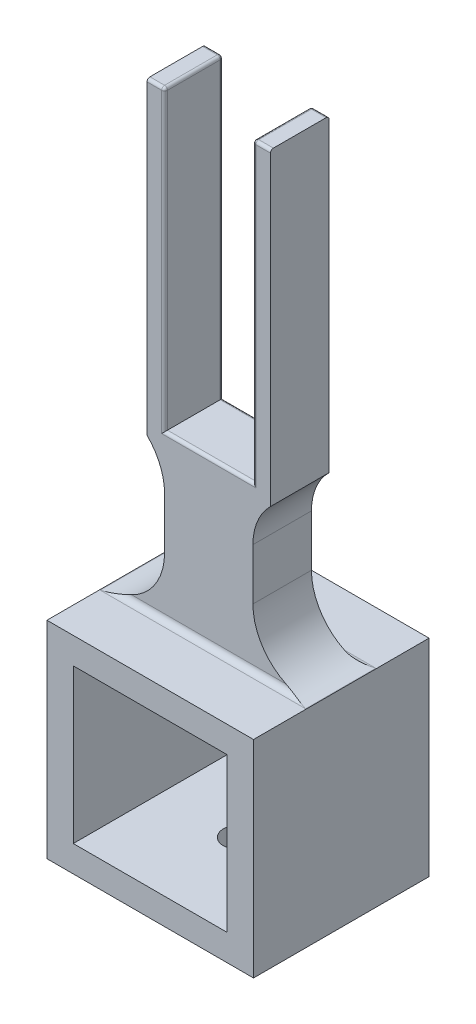
SolidWorks part; units mm, degrees
ref_plane "Front Plane" through (0, 0, 0) normal (0, 0, 1) x (1, 0, 0)
ref_plane "Top Plane" through (0, 0, 0) normal (0, 1, 0) x (1, 0, 0)
ref_plane "Right Plane" through (0, 0, 0) normal (1, 0, 0) x (0, 0, -1)
sketch "Sketch1" plane through (0, 0, 0) normal (0, 0, 1) x (1, 0, 0)
  line L0 (-12.5, -83.55) -> (-12.5, -58.55) construction
  line L1 (12.5, -83.55) -> (-12.5, -83.55) construction
  line L2 (12.5, -58.55) -> (12.5, -83.55) construction
  line L3 (-12.5, -58.55) -> (12.5, -58.55) construction
  line L4 (-12.65, -83.7) -> (-12.65, -58.4)
  line L5 (-12.65, -58.4) -> (12.65, -58.4)
  line L6 (12.65, -58.4) -> (12.65, -83.7)
  line L7 (12.65, -83.7) -> (-12.65, -83.7)
  line L8 (-17.65, -88.7) -> (-17.65, -53.4)
  line L9 (-17.65, -53.4) -> (17.65, -53.4)
  line L10 (17.65, -53.4) -> (17.65, -88.7)
  line L11 (17.65, -88.7) -> (-17.65, -88.7)
  line L12 (-5.55, 5.55) -> (5.55, 5.55)
  line L13 (-5.35, 5.35) -> (5.35, 5.35) construction
  line L14 (-5.35, 5.35) -> (-5.35, -15.25) construction
  line L15 (-5.35, -15.25) -> (5.35, -15.25) construction
  line L16 (5.35, 5.35) -> (5.35, -15.25) construction
  line L17 (5.55, 5.55) -> (5.55, -15.45)
  line L18 (-5.55, -15.45) -> (5.55, -15.45)
  line L19 (-5.55, 5.55) -> (-5.55, -15.45)
  line L20 (7.55, -53.4) -> (-7.55, -53.4)
  line L21 (7.55, -53.4) -> (7.55, 8.55)
  line L22 (7.55, 8.55) -> (-7.55, 8.55)
  line L23 (-7.55, -53.4) -> (-7.55, 8.55)
  circle A0 centre (0, 0) radius 5.35 construction
  circle A1 centre (0, 0) radius 5.55
  point P28 (0, 8.55)
  point P29 (0, -53.4)
  point P30 (0, -88.7)
sketch "Sketch2" plane through (0, 0, 0) normal (0, 0, 1) x (1, 0, 0)
  line L0 (-5.55, -15.45) -> (5.55, -15.45) construction
  line L1 (5.55, 5.55) -> (5.55, -15.45) construction
  line L2 (-5.55, 5.55) -> (5.55, 5.55) construction
  line L3 (-5.55, 5.55) -> (-5.55, -15.45) construction
  line L4 (-7.55, -53.4) -> (-7.55, 8.55) construction
  line L5 (7.55, 8.55) -> (-7.55, 8.55) construction
  line L6 (7.55, -53.4) -> (7.55, 8.55) construction
  line L8 (-17.65, -53.4) -> (17.65, -53.4) construction
  line L9 (17.65, -53.4) -> (17.65, -88.7) construction
  line L10 (17.65, -88.7) -> (-17.65, -88.7) construction
  line L11 (-17.65, -88.7) -> (-17.65, -53.4) construction
  line L12 (-5.55, -15.45) -> (5.55, -15.45) construction
  line L13 (5.55, 5.55) -> (5.55, -15.45) construction
  line L14 (-5.55, 5.55) -> (5.55, 5.55) construction
  line L15 (-5.55, 5.55) -> (-5.55, -15.45) construction
  line L16 (-7.55, -53.4) -> (-7.55, 8.55)
  line L17 (7.55, 8.55) -> (-7.55, 8.55)
  line L18 (7.55, -53.4) -> (7.55, 8.55)
  line L20 (-17.65, -53.4) -> (-7.55, -53.4)
  line L21 (17.65, -53.4) -> (17.65, -88.7)
  line L22 (17.65, -88.7) -> (-17.65, -88.7)
  line L23 (-17.65, -88.7) -> (-17.65, -53.4)
  line L24 (-12.65, -83.7) -> (-12.65, -58.4) construction
  line L25 (-12.65, -58.4) -> (12.65, -58.4) construction
  line L26 (12.65, -58.4) -> (12.65, -83.7) construction
  line L27 (12.65, -83.7) -> (-12.65, -83.7) construction
  line L28 (-12.65, -83.7) -> (-12.65, -58.4)
  line L29 (-12.65, -58.4) -> (12.65, -58.4)
  line L30 (12.65, -58.4) -> (12.65, -83.7)
  line L31 (12.65, -83.7) -> (-12.65, -83.7)
  line L32 (7.55, -53.4) -> (17.65, -53.4)
  line L33 (0, -5.55) -> (0, -5.35) construction
  line L34 (0, -5.35) -> (0, -5.475)
  circle A0 centre (0, 0) radius 5.35 construction
  circle A1 centre (0, 0) radius 5.55 construction
  circle A2 centre (0, 0) radius 5.35 construction
  circle A3 centre (0, 0) radius 5.55 construction
  circle A4 centre (0, 0) radius 5.475 construction
  dimension "D1" = 0.125
extrude "Boss-Extrude1" add sketch "Sketch2" along normal mid plane 30 contours L32 L18 L17 L16 L20 L23 L22 L21 A4 L30 L31 L28 L29 region at (0, -41.5413, 0)
sketch "Sketch3" plane through (7.55, 0, 0) normal (1, 0, 0) x (0, 0, -1)
  line L0 (-15, 8.55) -> (15, 8.55) construction
  line L1 (-5, 8.55) -> (5, 8.55) construction
  line L2 (-5, 8.55) -> (-5, -53.4) construction
  line L3 (-5, -53.4) -> (5, -53.4) construction
  line L4 (5, 8.55) -> (5, -53.4) construction
  line L5 (-15, -53.4) -> (15, -53.4) construction
  line L8 (-5, 8.55) -> (-15, 8.55)
  line L10 (-5, 8.55) -> (-5, -53.4)
  line L11 (-5, -53.4) -> (-15, -53.4)
  line L12 (-15, 8.55) -> (-15, -53.4)
  line L13 (5, 8.55) -> (15, 8.55)
  line L14 (5, 8.55) -> (5, -53.4)
  line L15 (5, -53.4) -> (15, -53.4)
  line L16 (15, 8.55) -> (15, -53.4)
  point P8 (0, 8.55)
  point P9 (0, 8.55)
  dimension "D1" = 10
extrude "Cut-Extrude1" cut sketch "Sketch3" against normal through all both and the other way through all
sketch "Sketch7" plane through (0, 0, 5) normal (0, 0, 1) x (1, 0, 0)
  line L0 (0, 0) -> (0, 6.8) construction
  circle A1 centre (0, 6.8) radius 5.475
  circle A3 centre (0, 0) radius 5.475 construction
  circle A5 centre (0, -6.8) radius 5.475
  point P10 (0, 0)
sketch "Sketch8" plane through (0, 0, 5) normal (0, 0, 1) x (1, 0, 0)
  line L0 (5.55, 22.325) -> (-5.55, 22.325)
  line L1 (5.55, 1.325) -> (5.55, 22.325)
  line L2 (-5.55, 1.325) -> (5.55, 1.325)
  line L3 (-5.55, 22.325) -> (-5.55, 1.325)
  line L5 (10.55, -25.325) -> (-10.55, -25.325)
  line L6 (10.55, -25.325) -> (10.55, 25.325)
  line L7 (10.55, 25.325) -> (-10.55, 25.325)
  line L8 (5.55, -1.325) -> (-5.55, -1.325)
  line L9 (5.55, -22.325) -> (5.55, -1.325)
  line L10 (-5.55, -22.325) -> (5.55, -22.325)
  line L11 (-5.55, -1.325) -> (-5.55, -22.325)
  line L12 (-10.55, -25.325) -> (-10.55, 25.325)
  line L14 (-7.55, 8.55) -> (-7.55, -43.4)
  line L16 (7.55, 8.55) -> (7.55, -43.4)
  line L17 (-7.4, 8.55) -> (-7.4, -43.4)
  line L18 (7.4, 8.55) -> (7.4, -43.4)
  circle A3 centre (0, -6.8) radius 5.475
  circle A5 centre (0, 6.8) radius 5.475
fillet "Fillet1" radius 10 2 edges at (-7.55, -53.4, 0) (7.55, -53.4, 0)
fillet "Fillet2" radius 1 2 edges at (0, -53.4, 5) (0, -53.4, -5)
sketch "Sketch4" plane through (0, -88.7, 0) normal (0, -1, 0) x (1, 0, 0)
  line L0 (2.6847, 4.65) -> (-2.6847, 4.65)
  line L1 (2.5981, 4.5) -> (-2.5981, 4.5) construction
  line L2 (-2.5981, 4.5) -> (-5.1962, 0) construction
  line L3 (-5.1962, 0) -> (-2.5981, -4.5) construction
  line L4 (-2.5981, -4.5) -> (2.5981, -4.5) construction
  line L5 (2.5981, -4.5) -> (5.1962, 0) construction
  line L6 (5.1962, 0) -> (2.5981, 4.5) construction
  line L7 (-2.6847, 4.65) -> (-5.3694, 0)
  line L8 (-5.3694, 0) -> (-2.6847, -4.65)
  line L9 (-2.6847, -4.65) -> (2.6847, -4.65)
  line L10 (2.6847, -4.65) -> (5.3694, 0)
  line L11 (5.3694, 0) -> (2.6847, 4.65)
  circle A0 centre (0, 0) radius 2.5
  circle A1 centre (0, 0) radius 4.5 construction
  circle A2 centre (0, 0) radius 7.5
  dimension "D1" = 5
  dimension "D4" = 15
  dimension "D2" = 9
  dimension "D3" = 0.15
extrude "Boss-Extrude2" add sketch "Sketch4" along normal blind 5 contours A2 L11 L10 L9 L8 L7 L0 region at (-7.2879, -88.7, 0)
fillet "Fillet3" radius 1 1 edges at (7.5, -88.7, 0)
sketch "Sketch5" plane through (0, -88.7, 0) normal (0, -1, 0) x (1, 0, 0)
  circle A0 centre (0, 0) radius 2.5
  dimension "D1" = 5
extrude "Cut-Extrude2" cut sketch "Sketch5" against normal up to next
sketch "Sketch9" plane through (0, 0, 5) normal (0, 0, 1) x (1, 0, 0)
  line L0 (-7.4, 8.55) -> (-7.4, -43.4) construction
  line L1 (-7.4, 8.55) -> (-7.4, -25.475)
  line L2 (7.4, 8.55) -> (7.4, -43.4) construction
  line L3 (7.4, 8.55) -> (7.4, -25.475)
  line L4 (7.55, 8.55) -> (7.55, -43.4) construction
  line L5 (7.55, 25.325) -> (7.55, -25.475)
  line L6 (-7.55, 8.55) -> (-7.55, -43.4) construction
  line L7 (-7.55, 25.325) -> (-7.55, -25.475)
  line L8 (10.55, -25.325) -> (-10.55, -25.325) construction
  line L9 (10.55, -25.325) -> (-10.55, -25.325) construction
  line L10 (7.55, -25.475) -> (-7.55, -25.475)
  line L14 (-10.55, -25.325) -> (-10.55, 25.325) construction
  line L15 (-10.55, -25.325) -> (-10.55, 25.325)
  line L16 (10.55, 25.325) -> (-10.55, 25.325) construction
  line L17 (10.55, -25.325) -> (10.55, 25.325) construction
  line L18 (10.55, 25.325) -> (7.55, 25.325)
  line L19 (10.55, -25.325) -> (10.55, 25.325)
  line L20 (-7.55, 25.325) -> (-10.55, 25.325)
  line L21 (10.55, -27.475) -> (-10.55, -27.475)
  line L22 (-10.55, -25.325) -> (-10.55, -27.475)
  line L23 (10.55, -25.325) -> (10.55, -27.475)
  line L24 (10.55, -25.475) -> (-10.55, -25.475) construction
  line M15 (7.55, -43.4) -> (7.55, 8.55)
  line M17 (-7.55, 8.55) -> (-7.55, -43.4)
  dimension "D1" = 0.15
  dimension "D2" = 2
extrude "Boss-Extrude3" add sketch "Sketch9" against normal up to surface (10 mm away) contours L15 L22 L21 L7 L20 M17 | L23 L19 L18 L5 L21 M15 | L21 L10 M15 M17 region at (9.05, -1.075, 5) region at (0, -26.475, 5) region at (-9.05, -1.075, 5) up to face at (0, -29.3536, -5)
fillet "Fillet4" radius 10 2 edges at (-7.55, -27.475, 0) (7.55, -27.475, 0)
sketch "Sketch10" plane through (0, 0, 5) normal (0, 0, 1) x (1, 0, 0)
  line L0 (-7.4, 8.55) -> (-7.4, -43.4) construction
  line L1 (-7.4, 8.55) -> (-7.4, -25.325)
  line L2 (7.4, 8.55) -> (7.4, -43.4) construction
  line L3 (7.4, 8.55) -> (7.4, -25.325)
  line L4 (-7.55, 8.55) -> (7.55, 8.55) construction
  line L5 (-7.4, 8.55) -> (7.4, 8.55)
  line L6 (10.55, -25.325) -> (-10.55, -25.325) construction
  line L7 (7.4, -25.325) -> (-7.4, -25.325)
sketch "Sketch11" plane through (0, 8.55, 0) normal (0, 1, 0) x (1, 0, 0)
  line L4 (-7.55, 5) -> (-7.55, -5)
  line L5 (-7.55, -5) -> (7.55, -5)
  line L6 (7.55, -5) -> (7.55, 5)
  line L7 (7.55, 5) -> (-7.55, 5)
  line L8 (-7.55, 5) -> (-7.55, -5)
  line L9 (-7.55, -5) -> (7.55, -5)
  line L10 (7.55, -5) -> (7.55, 5)
  line L11 (7.55, 5) -> (-7.55, 5)
  dimension "D1" = 0
extrude "Cut-Extrude4" cut sketch "Sketch11" against normal up to vertex (34.025 mm away) up to point (7.55, -25.475, 5)
fillet "Fillet5" radius 0.5 6 edges at (7.55, -0.075, -5) (0, -25.475, -5) (-7.55, -0.075, -5) (7.55, -0.075, 5) (0, -25.475, 5) (-7.55, -0.075, 5)
fillet "Fillet6" radius 0.5 10 edges at (-9.3, 25.325, -5) (-7.6964, 25.325, -4.8536) (-9.3, 25.325, 5) (-7.6964, 25.325, 4.8536) (9.3, 25.325, -5) (7.6964, 25.325, -4.8536) (9.3, 25.325, 5) (7.6964, 25.325, 4.8536) (-7.55, 25.325, 0) (7.55, 25.325, 0)
sketch "Sketch12" plane through (0, 0, 15) normal (0, 0, 1) x (1, 0, 0)
  line L0 (-12.65, -83.7) -> (-12.65, -58.4) construction
  line L1 (12.65, -83.7) -> (-12.65, -83.7) construction
  line L2 (12.65, -58.4) -> (12.65, -83.7) construction
  line L3 (-12.65, -58.4) -> (12.65, -58.4) construction
  line L4 (-12.65, -83.7) -> (-12.65, -58.4) construction
  line L5 (12.65, -83.7) -> (-12.65, -83.7) construction
  line L6 (12.65, -58.4) -> (12.65, -83.7) construction
  line L7 (-12.65, -58.4) -> (12.65, -58.4) construction
  line L8 (-13.15, -57.9) -> (13.15, -57.9)
  line L9 (13.15, -57.9) -> (13.15, -84.2)
  line L10 (13.15, -84.2) -> (-13.15, -84.2)
  line L11 (-13.15, -84.2) -> (-13.15, -57.9)
  dimension "D1" = 0.5
extrude "Cut-Extrude5" cut sketch "Sketch12" against normal through all both and the other way through all
